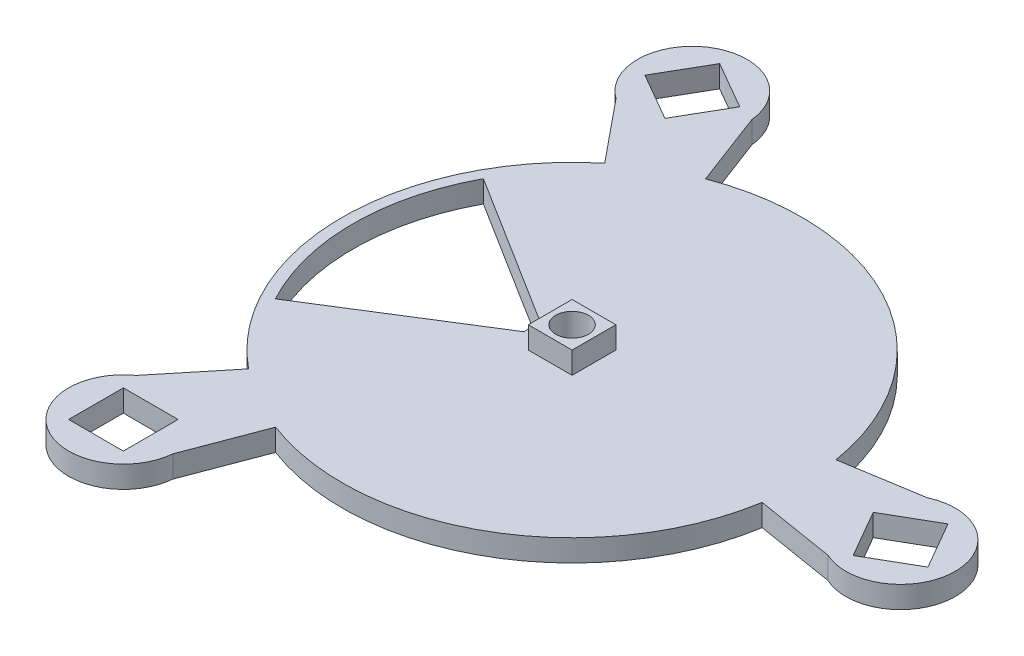
SolidWorks part; units mm, degrees
ref_plane "Front Plane" through (0, 0, 0) normal (0, 0, 1) x (1, 0, 0)
ref_plane "Top Plane" through (0, 0, 0) normal (0, 1, 0) x (1, 0, 0)
ref_plane "Right Plane" through (0, 0, 0) normal (1, 0, 0) x (0, 0, -1)
sketch "Sketch1" plane through (0, 0, 0) normal (0, 1, 0) x (1, 0, 0)
  line L0 (0, 0) -> (-15, -25.9808) construction
  line L4 (-17.5, -23.4808) -> (-12.5, -23.4808)
  line L5 (-17.5, -23.4808) -> (-17.5, -28.4808)
  line L6 (-17.5, -28.4808) -> (-12.5, -28.4808)
  line L7 (-12.5, -23.4808) -> (-12.5, -28.4808)
  line L8 (0, 0) -> (-17.8866, -21.8982)
  line L15 (0, 0) -> (-10.0211, -26.4394)
  line L16 (-11.5849, 26.8958) -> (-14.0849, 22.5657)
  line L17 (-11.5849, 26.8958) -> (-15.9151, 29.3958)
  line L18 (-15.9151, 29.3958) -> (-18.4151, 25.0657)
  line L19 (-14.0849, 22.5657) -> (-18.4151, 25.0657)
  line L20 (0, 0) -> (-10.0211, 26.4394)
  line L21 (0, 0) -> (-15, 25.9808) construction
  line L22 (0, 0) -> (-17.8866, 21.8982)
  line L23 (29.0849, -3.4151) -> (26.5849, 0.9151)
  line L24 (29.0849, -3.4151) -> (33.4151, -0.9151)
  line L25 (33.4151, -0.9151) -> (30.9151, 3.4151)
  line L26 (26.5849, 0.9151) -> (30.9151, 3.4151)
  line L27 (0, 0) -> (27.9077, -4.5412)
  line L28 (0, 0) -> (30, 0) construction
  line L29 (0, 0) -> (27.9077, 4.5412)
  line L30 (0, 0) -> (0, -21) construction
  circle A0 centre (0, 0) radius 21
  arc A1 (-17.8866, -21.8982) -> (-10.0211, -26.4394) centre (-15, -25.9808) ccw
  arc A2 (-10.0211, 26.4394) -> (-17.8866, 21.8982) centre (-15, 25.9808) ccw
  arc A3 (27.9077, -4.5412) -> (27.9077, 4.5412) centre (30, 0) ccw
  point P8 (-15, -28.4808)
  point P9 (-17.5, -25.9808)
  point P29 (0, 0)
  dimension "D1" = 42
  dimension "D5" = 5
  dimension "D2" = 30
  dimension "D3" = 5
  dimension "D4" = 28.2748
  dimension "D6" = 3
  dimension "D7" = 120
  dimension "D8" = 120
  dimension "D9" = 120
  dimension "D10" = 30
extrude "Boss-Extrude1" add sketch "Sketch1" along normal blind 2 contours L8 A1 L15 A0 L4 L7 L6 L5 | L27 A3 L29 A0 L23 L26 L25 L24 | L20 A2 L22 A0 L16 L19 L18 L17 | A0 region at (-10.5967, 0, 18.3541) region at (-10.5967, 0, -18.3541) region at (21.1054, 0, 1.7059)
ref_plane "Plane1" through (0, 2, 0) normal (0, 1, 0) x (1, 0, 0)
sketch "Sketch2" plane through (0, 2, 0) normal (0, 1, 0) x (1, 0, 0)
  line L1 (-2, 2) -> (2, 2)
  line L2 (-2, 2) -> (-2, -2)
  line L3 (-2, -2) -> (2, -2)
  line L4 (2, 2) -> (2, -2)
  point P4 (0, -2)
  point P6 (-2, 0)
  dimension "D1" = 4
extrude "Boss-Extrude2" add sketch "Sketch2" along normal blind 2
ref_plane "Plane2" through (0, 4, 0) normal (0, 1, 0) x (1, 0, 0)
sketch "Sketch3" plane through (0, 4, 0) normal (0, 1, 0) x (1, 0, 0)
  circle A0 centre (0, 0) radius 1.5
  dimension "D1" = 3
extrude "Cut-Extrude1" cut sketch "Sketch3" against normal up to next
sketch "Sketch4" plane through (0, 2, 0) normal (0, 1, 0) x (1, 0, 0)
  line L0 (0, 0) -> (-20, 0) construction
  line L1 (-3.6203, -0.735) -> (-17.5997, -9.5)
  line L2 (-3.6203, 0.735) -> (-17.5997, 9.5)
  arc A1 (-17.5997, 9.5) -> (-17.5997, -9.5) centre (0, 0) ccw
  arc A2 (-3.6203, 0.735) -> (-3.6203, -0.735) centre (0, 0) ccw
  point P1 (0, 0)
  dimension "D1" = 40
  dimension "D4" = 1.47
  dimension "D2" = 9.5
  dimension "D3" = 9.5
  dimension "D5" = 16.5
extrude "Cut-Extrude2" cut sketch "Sketch4" against normal up to next
